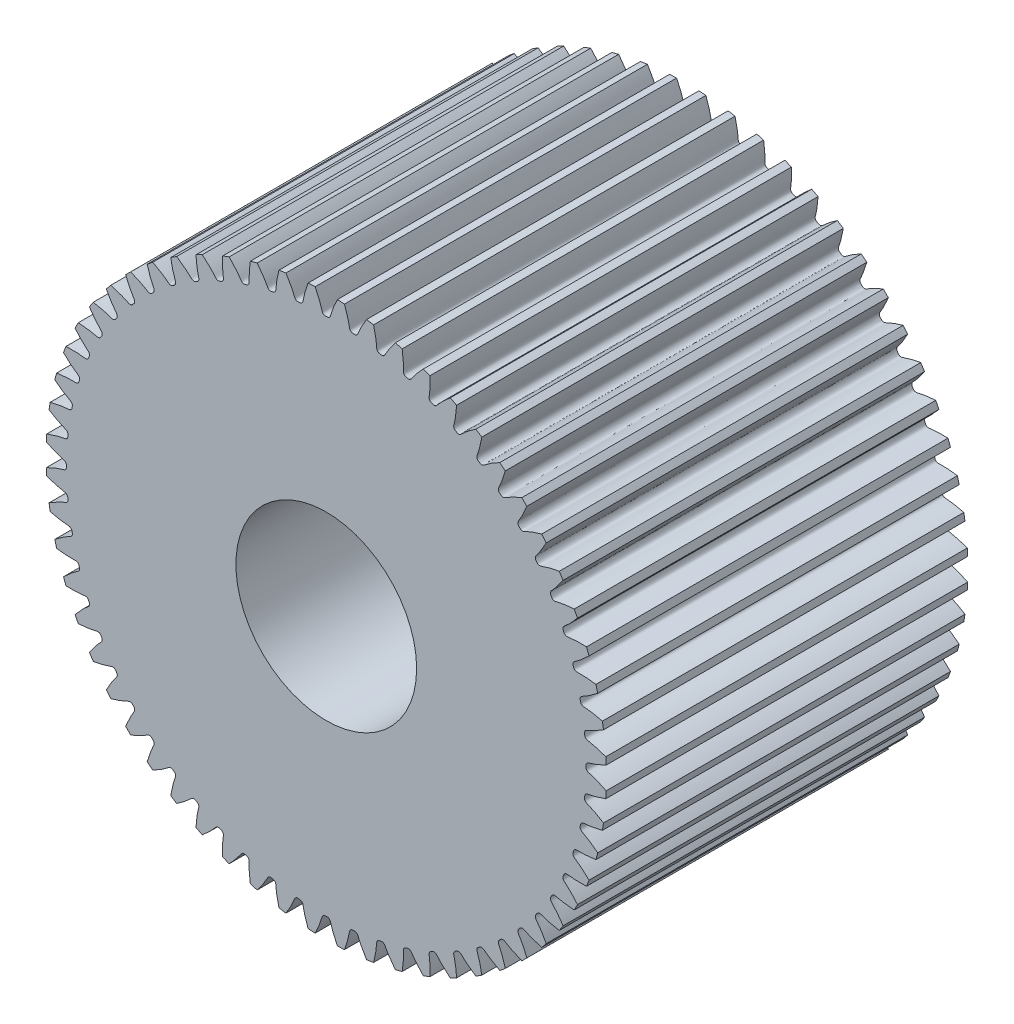
SolidWorks part; units mm, degrees
ref_plane "前视基准面" through (0, 0, 0) normal (0, 0, 1) x (1, 0, 0)
ref_plane "上视基准面" through (0, 0, 0) normal (0, 1, 0) x (1, 0, 0)
ref_plane "右视基准面" through (0, 0, 0) normal (1, 0, 0) x (0, 0, -1)
ref_axis "基准轴1" through (0, 0, 55) along (0, 0, -1)
sketch "SketchRevolveSpurGear2" plane through (0, 0, 0) normal (1, 0, 0) x (0, 0, -1)
  line L0 (0, 0) -> (1, 0) construction
  line L1 (-10, 0) -> (-10, 15.5)
  line L2 (-10, 15.5) -> (10, 15.5)
  line L3 (10, 15.5) -> (10, 0)
  line L4 (10, 0) -> (-10, 0)
revolve "SpurGear2" add sketch "SketchRevolveSpurGear2" angle 360 about L0
sketch "SketchToothSpurGear2" plane through (0, 0, 0) normal (0, 0, 1) x (1, 0, 0)
  arc A0 (15.5123, 0.6275) -> (15.5123, -0.6275) centre (0, 0) cw
  spline S0 degree 3 poles (15.5123, -0.6275) (15.4702, -0.6059) (15.4074, -0.5747) (15.3242, -0.535) (15.2638, -0.507) (15.2047, -0.4804) (15.1469, -0.4552) (15.0904, -0.4313) (15.0354, -0.4087) (14.9817, -0.3874) (14.9294, -0.3673) (14.8785, -0.3484) (14.8291, -0.3307) (14.7812, -0.3141) (14.7348, -0.2986) (14.6898, -0.2841) (14.6464, -0.2708) (14.5851, -0.2522) (14.5304, -0.2395) (14.4856, -0.2201) (14.4657, -0.2095) (14.4444, -0.1952) (14.4216, -0.175) (14.3983, -0.1454) (14.38, -0.1051) (14.373, -0.0545) (14.3761, 0) (14.373, 0.0545) (14.38, 0.1051) (14.3983, 0.1454) (14.4216, 0.175) (14.4444, 0.1952) (14.4657, 0.2095) (14.4856, 0.2201) (14.5304, 0.2395) (14.5851, 0.2522) (14.6464, 0.2708) (14.6898, 0.2841) (14.7348, 0.2986) (14.7812, 0.3141) (14.8291, 0.3307) (14.8785, 0.3484) (14.9294, 0.3673) (14.9817, 0.3874) (15.0354, 0.4087) (15.0904, 0.4313) (15.1469, 0.4552) (15.2047, 0.4804) (15.2638, 0.507) (15.3242, 0.535) (15.4074, 0.5747) (15.4702, 0.6059) (15.5123, 0.6275) knots 0 0 0 0 0.051766 0.076686 0.100963 0.124598 0.147592 0.169943 0.191651 0.212718 0.233143 0.252925 0.272065 0.290563 0.308419 0.325633 0.342204 0.358133 0.395729 0.403327 0.411415 0.420483 0.431261 0.444675 0.461387 0.478965 0.5 0.521035 0.538613 0.555325 0.568739 0.579517 0.588585 0.596673 0.604271 0.641867 0.657796 0.674367 0.691581 0.709437 0.727935 0.747075 0.766857 0.787282 0.808349 0.830057 0.852408 0.875402 0.899037 0.923314 0.948234 1 1 1 1
extrude "ToothExtrudeCutSpurGear2" cut sketch "SketchToothSpurGear2" against normal blind 10 and the other way blind 10
pattern_circular "PatternSpurGear2" count 60 every 6 about axis through (0, 0, 55) along (0, 0, -1) of "ToothExtrudeCutSpurGear2"
sketch "BoreRevolveSketch" plane through (0, 0, 0) normal (1, 0, 0) x (0, 0, -1)
  line L0 (0, 0) -> (1, 0) construction
  line L1 (-10, 0) -> (10, 0)
  line L2 (10, 0) -> (10, 5)
  line L3 (10, 5) -> (-10, 5)
  line L4 (-10, 5) -> (-10, 0)
  dimension "TaperSide1" = 5
  dimension "TaperSide2" = 5
revolve "BoreRevolveCut" cut sketch "BoreRevolveSketch" angle 360 about L0
sketch "AuxiliarySketchSpurGear2" plane through (0, 0, 0) normal (0, 0, 1) x (1, 0, 0)
  circle A0 centre (0, 0) radius 15 construction
  circle A1 centre (0, 0) radius 14.0954 construction
  circle A2 centre (0, 0) radius 14.5457 construction
  circle A3 centre (0, 0) radius 15.5 construction
  circle A4 centre (0, 0) radius 14.375 construction
  dimension "PitchDiameter" = 30
  dimension "BaseDiameter" = 28.1908
  dimension "FormDiameter" = 29.0915
  dimension "MajorDiameter" = 31
  dimension "MinorDiameter" = 28.75
